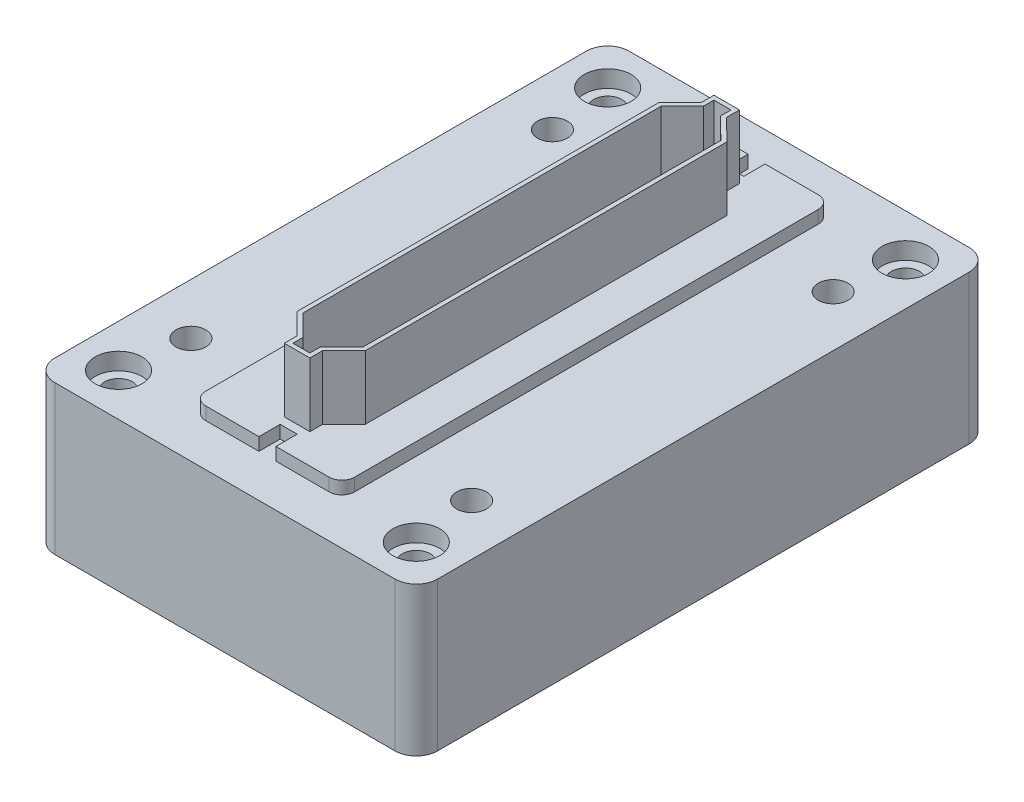
SolidWorks part; units mm, degrees
ref_plane "Front Plane" through (0, 0, 0) normal (0, 0, 1) x (1, 0, 0)
ref_plane "Top Plane" through (0, 0, 0) normal (0, 1, 0) x (1, 0, 0)
ref_plane "Right Plane" through (0, 0, 0) normal (1, 0, 0) x (0, 0, -1)
sketch "Sketch2" plane through (0, 0, 0) normal (0, 1, 0) x (1, 0, 0)
  line L1 (45, 67.5) -> (-45, 67.5)
  line L2 (45, 67.5) -> (45, -67.5)
  line L3 (45, -67.5) -> (-45, -67.5)
  line L4 (-45, 67.5) -> (-45, -67.5)
  line L5 (45, 67.5) -> (-45, -67.5) construction
  line L6 (45, -67.5) -> (-45, 67.5) construction
  point P0 (0, 0)
  dimension "D1" = 90
  dimension "D2" = 135
extrude "Boss-Extrude1" add sketch "Sketch2" along normal blind 35
fillet "Fillet1" radius 5 4 edges at (45, 17.5, -67.5) (45, 17.5, 67.5) (-45, 17.5, 67.5) (-45, 17.5, -67.5)
hole_wizard "CBORE for M6 Hex Head Bolt1" positions "3DSketch1" profile "Sketch6" counterbore size "M6" standard "DIN"
sketch3d "3DSketch1"
  line L1 (40, 35, -67.5) -> (-40, 35, -67.5) construction
  line L2 (-45, 35, -62.5) -> (-45, 35, 62.5) construction
  point P0 (-35, 35, -57.5)
  dimension "D1" = 10
  dimension "D2" = 10
sketch "Sketch6" plane through (-35, 35, -57.5) normal (1, 0, 0) x (0, 0, 1)
  line L0 (0, 0) -> (0, 43.9828)
  line L1 (0, 43.9828) -> (3.3, 42)
  line L2 (3.3, 42) -> (3.3, 4)
  line L3 (3.3, 4) -> (5.5, 4)
  line L4 (5.5, 4) -> (5.5, 0)
  line L5 (5.5, 0) -> (0, 0)
  line L10 (0, 43.9828) -> (-3.3, 42) construction
  line L11 (0, -6.35) -> (0, 107.95) construction
  dimension "Hole Dia." = 6.6
  dimension "Hole Depth" = 42
  dimension "C'Bore Dia." = 11
  dimension "C'Bore Depth" = 4
  dimension "Drill Angle" = 118
ref_axis "Axis1" through (0, -1.5, 0) along (0, 1, 0)
sketch "Sketch8" plane through (0, 35, 0) normal (0, 1, 0) x (1, 0, 0)
  line L0 (40, 67.5) -> (-40, 67.5) construction
  line L1 (-45, 62.5) -> (-45, -62.5) construction
  circle A0 centre (-33, 42.5) radius 3.5
  dimension "D1" = 7
  dimension "D2" = 25
  dimension "D3" = 12
extrude "Cut-Extrude1" cut sketch "Sketch8" against normal blind 10
mirror "Mirror1" about plane through (0, 0, 0) normal (1, 0, 0) of "Cut-Extrude1", "CBORE for M6 Hex Head Bolt1"
mirror "Mirror2" about plane through (0, 0, 0) normal (0, 0, 1) of "Mirror1"
sketch "Sketch9" plane through (0, 35, 0) normal (0, 1, 0) x (1, 0, 0)
  line L0 (0, 0) -> (17.5, 0) construction
  line L1 (14.5, -57.5) -> (2, -57.5)
  line L2 (17.5, -54.5) -> (17.5, 54.5)
  line L3 (14.5, 57.5) -> (2, 57.5)
  line L4 (-17.5, -54.5) -> (-17.5, 54.5)
  line L5 (17.5, -57.5) -> (-17.5, 57.5) construction
  line L6 (17.5, 57.5) -> (-17.5, -57.5) construction
  line L8 (-2, 57.5) -> (-2, 52.5)
  line L9 (-2, 52.5) -> (2, 52.5)
  line L10 (2, 57.5) -> (2, 52.5)
  line L11 (-2, 57.5) -> (2, 52.5) construction
  line L12 (-2, 52.5) -> (2, 57.5) construction
  line L13 (-2, -57.5) -> (-2, -52.5)
  line L14 (-2, -52.5) -> (2, -52.5)
  line L15 (2, -57.5) -> (2, -52.5)
  line L16 (-2, 57.5) -> (-14.5, 57.5)
  line L17 (-2, -57.5) -> (-14.5, -57.5)
  arc A0 (-14.5, 57.5) -> (-17.5, 54.5) centre (-14.5, 54.5) ccw
  arc A1 (17.5, 54.5) -> (14.5, 57.5) centre (14.5, 54.5) ccw
  arc A2 (14.5, -57.5) -> (17.5, -54.5) centre (14.5, -54.5) ccw
  arc A3 (-14.5, -57.5) -> (-17.5, -54.5) centre (-14.5, -54.5) cw
  point P0 (0, 0)
  point P18 (0, 55)
  dimension "D3" = 3
  dimension "D1" = 115
  dimension "D2" = 35
  dimension "D4" = 4
  dimension "D5" = 5
extrude "Boss-Extrude2" add sketch "Sketch9" along normal blind 3 separate body
sketch "Sketch10" plane through (0, 38, 0) normal (0, 1, 0) x (1, 0, 0)
  line L0 (2.9753, 47.5) -> (8, 42.5)
  line L2 (8, -42.5) -> (8, 42.5)
  line L4 (-8, -42.5) -> (-8, 42.5)
  line L5 (8, -42.5) -> (-8, 42.5) construction
  line L6 (8, 42.5) -> (-8, -42.5) construction
  line L7 (-3.0247, 50.5) -> (2.9753, 50.5)
  line L8 (-3.0247, 50.5) -> (-3.0247, 47.5)
  line L10 (2.9753, 50.5) -> (2.9753, 47.5)
  line L11 (-3.0247, 50.5) -> (2.9753, 44.2507) construction
  line L12 (-3.0247, 44.2507) -> (2.9753, 50.5) construction
  line L13 (-3.0247, 47.5) -> (-8, 42.5)
  line L14 (0, 0) -> (8, 0) construction
  line L15 (-3.0247, -47.5) -> (-8, -42.5)
  line L16 (-3.0247, -50.5) -> (-3.0247, -47.5)
  line L17 (2.9753, -47.5) -> (8, -42.5)
  line L18 (2.9753, -50.5) -> (2.9753, -47.5)
  line L19 (-3.0247, -50.5) -> (2.9753, -50.5)
  line L20 (7, -42.0843) -> (7, 42.0843)
  line L21 (1.9753, 47.0843) -> (7, 42.0843)
  line L22 (1.9753, 49.5) -> (1.9753, 47.0843)
  line L23 (-2.0247, 49.5) -> (1.9753, 49.5)
  line L24 (-2.0247, 49.5) -> (-2.0247, 47.0872)
  line L25 (-2.0247, 47.0872) -> (-7, 42.0872)
  line L26 (-7, -42.0872) -> (-7, 42.0872)
  line L27 (-2.0247, -47.0872) -> (-7, -42.0872)
  line L28 (-2.0247, -49.5) -> (-2.0247, -47.0872)
  line L29 (-2.0247, -49.5) -> (1.9753, -49.5)
  line L30 (1.9753, -49.5) -> (1.9753, -47.0843)
  line L31 (1.9753, -47.0843) -> (7, -42.0843)
  point P0 (0, 0)
  point P6 (-0.0247, 47.3753)
  dimension "D1" = 6
  dimension "D2" = 85
  dimension "D3" = 16
  dimension "D4" = 1
  dimension "D5" = 3
extrude "Boss-Extrude3" add sketch "Sketch10" along normal blind 15
